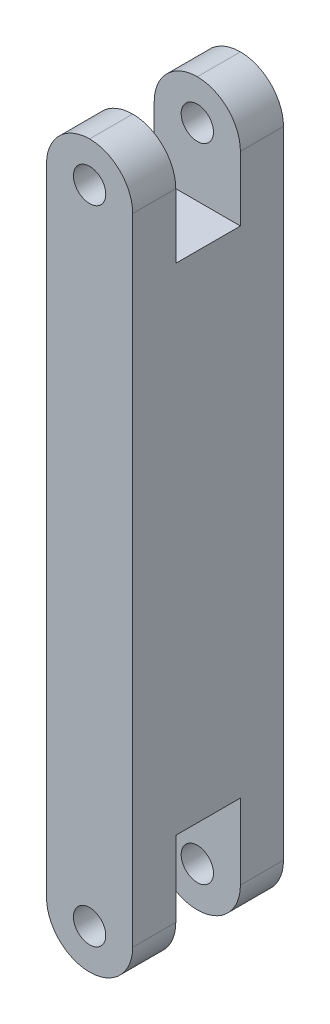
SolidWorks part; units mm, degrees
ref_plane "Front" through (0, 0, 0) normal (0, 0, 1) x (1, 0, 0)
ref_plane "Top" through (0, 0, 0) normal (0, 1, 0) x (1, 0, 0)
ref_plane "Right" through (0, 0, 0) normal (1, 0, 0) x (0, 0, -1)
sketch "Sketch1" plane through (0, 0, 0) normal (0, 0, 1) x (1, 0, 0)
  line L1 (-4, -33.495) -> (4, -33.495)
  line L2 (-4, -33.495) -> (-4, 33.495)
  line L3 (-4, 33.495) -> (4, 33.495)
  line L4 (4, -33.495) -> (4, 33.495)
  line L5 (-4, -33.495) -> (4, 33.495) construction
  line L6 (-4, 33.495) -> (4, -33.495) construction
  circle A0 centre (0, 29.795) radius 1.5
  circle A1 centre (0, -29.795) radius 1.5
  point P0 (0, 0)
  dimension "D3" = 3
  dimension "D4" = 3
  dimension "D1" = 3.7
  dimension "D2" = 8
  dimension "D5" = 29.795
  dimension "D6" = 29.795
extrude "Boss-Extrude1" add sketch "Sketch1" along normal blind 14
fillet "Fillet1" radius 4 4 edges at (-4, -33.495, 7) (4, -33.495, 7) (-4, 33.495, 7) (4, 33.495, 7)
sketch "Sketch2" plane through (-4, 0, 0) normal (-1, 0, 0) x (0, 0, 1)
  line L0 (14, 33.495) -> (0, 33.495) construction
  line L1 (4, 33.495) -> (10, 33.495)
  line L2 (4, 33.495) -> (4, 23.495)
  line L3 (4, 23.495) -> (10, 23.495)
  line L4 (10, 33.495) -> (10, 23.495)
  line L5 (4, 33.495) -> (10, 23.495) construction
  line L6 (4, 23.495) -> (10, 33.495) construction
  line L7 (14, 29.495) -> (14, -29.495) construction
  line L8 (0, -33.495) -> (14, -33.495) construction
  line L9 (4, -33.495) -> (10, -33.495)
  line L10 (4, -33.495) -> (4, -22.495)
  line L11 (4, -22.495) -> (10, -22.495)
  line L12 (10, -33.495) -> (10, -22.495)
  line L13 (4, -33.495) -> (10, -22.495) construction
  line L14 (4, -22.495) -> (10, -33.495) construction
  point P4 (7, 28.495)
  point P13 (7, -27.995)
  dimension "D1" = 10
  dimension "D2" = 6
  dimension "D3" = 4
  dimension "D4" = 11
  dimension "D5" = 6
  dimension "D6" = 4
extrude "Cut-Extrude1" cut sketch "Sketch2" against normal through all
